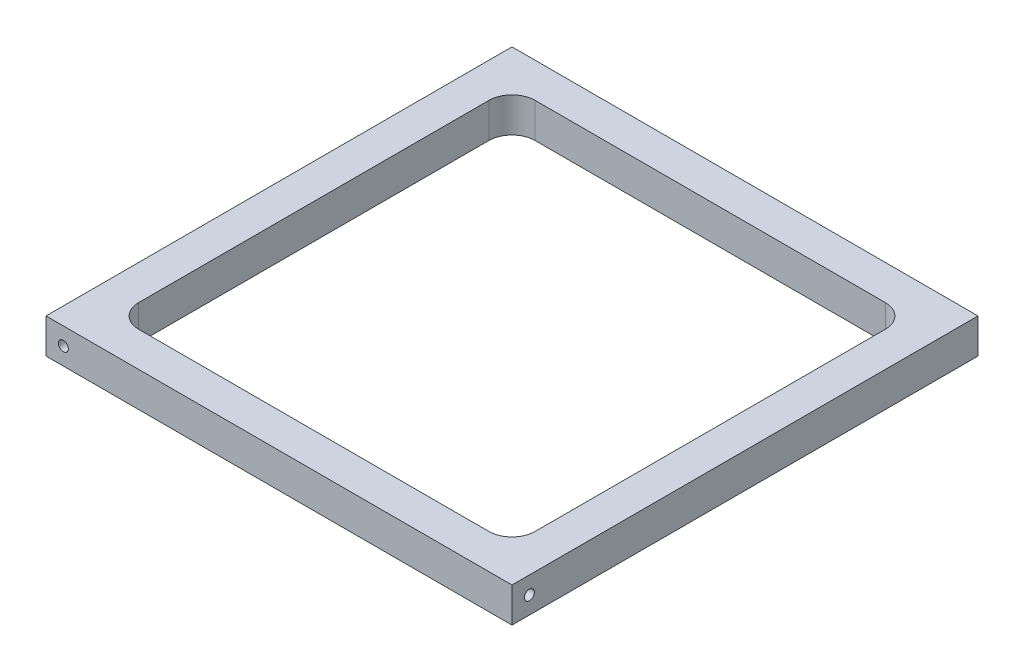
SolidWorks part; units mm, degrees
material "6061-T6 (SS)"
ref_plane "Front Plane" through (0, 0, 0) normal (0, 0, 1) x (1, 0, 0)
ref_plane "Top Plane" through (0, 0, 0) normal (0, 1, 0) x (1, 0, 0)
ref_plane "Right Plane" through (0, 0, 0) normal (1, 0, 0) x (0, 0, -1)
sketch "Sketch1" plane through (0, 0, 0) normal (0, 1, 0) x (1, 0, 0)
  line L5 (0, 0) -> (127.635, 0)
  line L6 (0, 0) -> (0, 127.635)
  line L7 (0, 127.635) -> (127.635, 127.635)
  line L8 (127.635, 0) -> (127.635, 127.635)
  dimension "D1" = 127.635
  dimension "D2" = 127.635
extrude "Boss-Extrude1" add sketch "Sketch1" along normal blind 9.525 contours L5 L8 L7 L6
sketch "Sketch5" plane through (0, 9.525, 0) normal (0, 1, 0) x (1, 0, 0)
  line L0 (63.8175, 127.635) -> (63.8175, 0) construction
  line L1 (0, 127.635) -> (127.635, 127.635) construction
  line L2 (0, 0) -> (127.635, 0) construction
  line L4 (9.525, 118.11) -> (118.11, 118.11)
  line L5 (9.525, 118.11) -> (9.525, 9.525)
  line L6 (9.525, 9.525) -> (118.11, 9.525)
  line L7 (118.11, 118.11) -> (118.11, 9.525)
  line L8 (9.525, 118.11) -> (118.11, 9.525) construction
  line L9 (9.525, 9.525) -> (118.11, 118.11) construction
  point P6 (63.8175, 63.8175)
  dimension "D1" = 108.585
  dimension "D2" = 108.585
extrude "Cut-Extrude1" cut sketch "Sketch5" against normal blind 9.525 contours L5 L4 L7 L6
fillet "Fillet1" radius 6.35 4 edges at (118.11, 4.7625, -9.525) (118.11, 4.7625, -118.11) (9.525, 4.7625, -118.11) (9.525, 4.7625, -9.525)
sketch "Sketch6" plane through (127.635, 0, 0) normal (1, 0, 0) x (0, 0, -1)
  circle A0 centre (4.7625, 4.7625) radius 1.3589
  dimension "D1" = 2.7178
extrude "tapped hole" cut sketch "Sketch6" against normal blind 6.35
sketch "Sketch7" plane through (0, 0, -127.635) normal (0, 0, -1) x (-1, 0, 0)
  circle A0 centre (-122.8725, 4.7625) radius 1.3525
  dimension "D1" = 2.7051
sketch "Sketch8" plane through (0, 0, 0) normal (-1, 0, 0) x (0, 0, 1)
  circle A0 centre (-122.8725, 4.7625) radius 1.3525
  dimension "D1" = 2.7051
sketch "Sketch9" plane through (0, 0, 0) normal (0, 0, 1) x (1, 0, 0)
  circle A0 centre (4.7625, 4.7625) radius 1.3526
  dimension "D1" = 2.7051
extrude "Cut-Extrude3" cut sketch "Sketch7" against normal blind 6.35
extrude "Cut-Extrude4" cut sketch "Sketch8" against normal blind 6.35
extrude "Cut-Extrude5" cut sketch "Sketch9" against normal blind 6.35
